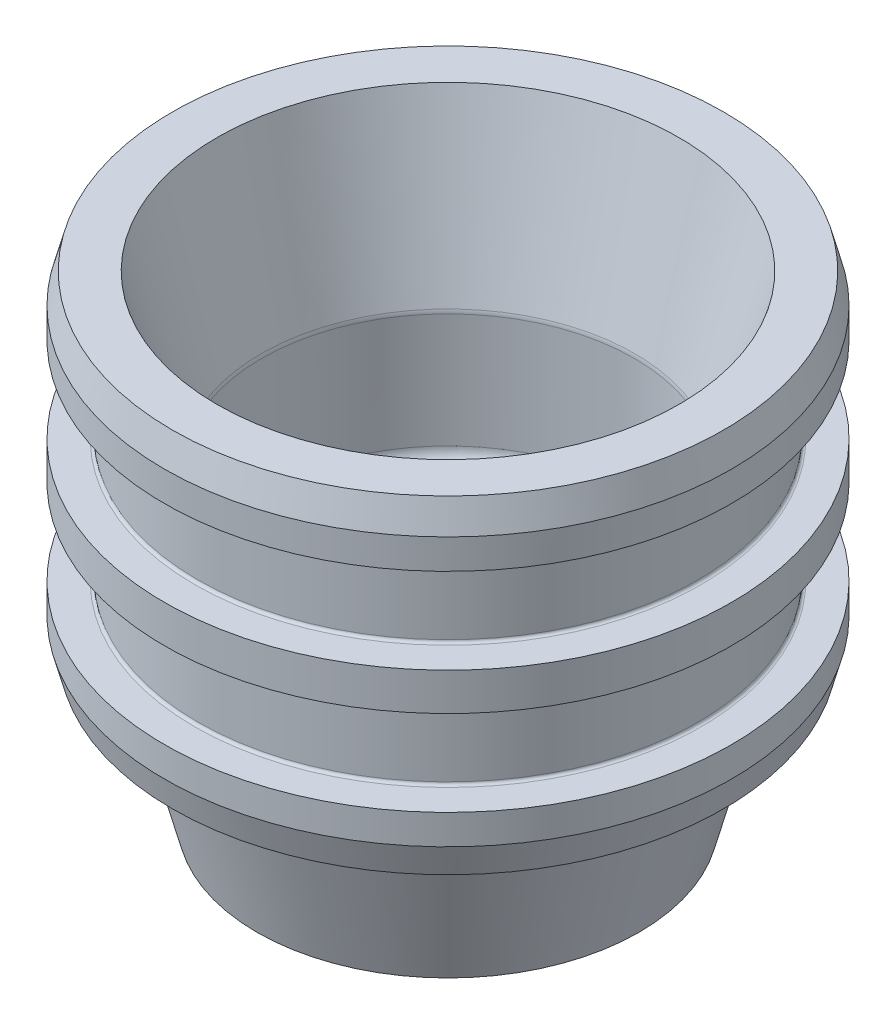
SolidWorks part; units mm, degrees
material "6063-T6"
ref_plane "Front Plane" through (0, 0, 0) normal (0, 0, 1) x (1, 0, 0)
ref_plane "Top Plane" through (0, 0, 0) normal (0, 1, 0) x (1, 0, 0)
ref_plane "Right Plane" through (0, 0, 0) normal (1, 0, 0) x (0, 0, -1)
sketch "Sketch1" plane through (0, 0, 0) normal (0, 1, 0) x (1, 0, 0)
  circle A0 centre (0, 0) radius 24.1554
  dimension "D1" = 48.3108
extrude "body" add sketch "Sketch1" along normal blind 40.64
sketch "Sketch2" plane through (0, 40.64, 0) normal (0, 1, 0) x (1, 0, 0)
  circle A0 centre (0, 0) radius 15.875
  dimension "D1" = 31.75
extrude "\"lightening hole\"" cut sketch "Sketch2" against normal blind 25.4
sketch "main-o-ring" plane through (0, 0, 0) normal (0, 0, 1) x (1, 0, 0)
  line L0 (0, 0) -> (0, 33.5592) construction
  line L1 (-24.1554, 35.56) -> (-24.1554, 28.2702)
  line L2 (-24.1554, 35.56) -> (-21.5508, 35.56)
  line L3 (-21.3106, 35.3198) -> (-21.3106, 28.5104)
  line L4 (-21.5508, 28.2702) -> (-24.1554, 28.2702)
  line L5 (24.1554, 40.64) -> (-24.1554, 40.64) construction
  line L6 (-22.7942, 40.64) -> (-24.1554, 35.56) construction
  line L7 (-24.1554, 35.56) -> (-24.1554, 40.64) construction
  line L8 (-24.1554, 40.64) -> (-22.7942, 40.64) construction
  arc A0 (-21.3106, 28.5104) -> (-21.5508, 28.2702) centre (-21.5508, 28.5104) cw
  arc A1 (-21.5508, 35.56) -> (-21.3106, 35.3198) centre (-21.5508, 35.3198) cw
  dimension "D5" = 0.2402
  dimension "D1" = 48.3108
  dimension "D2" = 7.2898
  dimension "D3" = 5.08
  dimension "D4" = 2.8448
  dimension "D6" = 15
  dimension "D7" = 5.08
revolve "o-ring-main (with backup rings)" cut sketch "main-o-ring" angle 360 about L0
chamfer "install-chamfer" distance 2.54 angle 15 1 edges at (0, 40.64, 24.1554) first distance on face at (0, 40.64, 24.1554)
chamfer "prop-chamfer" distance 3.81 angle 75 1 edges at (0, 40.64, 15.875) first distance on face at (0, 40.64, 23.4748)
ref_plane "mirror-plane" through (0, 26.67, 0) normal (0, 1, 0) x (1, 0, 0)
mirror "Top-Bottom Symmetry" about plane through (0, 26.67, 0) normal (0, 1, 0) of "o-ring-main (with backup rings)"
chamfer "bot-install-chamfer" [suppressed] distance 2.54 angle 15
chamfer "bot-prop-chamfer" [suppressed] distance 3.81 angle 75
hole_wizard "#6-32 Tapped Hole1" [suppressed] positions "3DSketch1" profile "Sketch3" tap size "#6-32" standard "ANSI Inch"
sketch3d "3DSketch1"
  point P0 (-24.1554, 7.9375, 0)
  dimension "D1" = 7.9375
sketch "Sketch3" plane through (-24.1554, 7.9375, 0) normal (0, 1, 0) x (0, 0, 1)
  line L0 (0, 0) -> (0, 8.7629)
  line L1 (0, 8.7629) -> (1.3525, 7.9502)
  line L2 (1.3525, 7.9502) -> (1.3525, 0)
  line L5 (1.3525, 0) -> (0, 0)
  line L10 (0, 8.7629) -> (-1.3526, 7.9502) construction
  line L11 (0, -6.35) -> (0, 107.95) construction
  dimension "Tap Drill Dia." = 2.7051
  dimension "Tap Drill Depth" = 7.9502
  dimension "Drill Angle" = 118
cosmetic thread "Hole Thread34" [suppressed] parameters "D1"=7.0104, "D2"=3.5052
ref_plane "Offset Reference" [suppressed] through (-22.3167, 0, -9.2439) normal (-0.9239, 0, -0.3827) x (0, -1, 0)
hole_wizard "#6-32 Tapped Hole2" [suppressed] positions "3DSketch2" profile "Sketch4" tap size "#6-32" standard "ANSI Inch"
sketch3d "3DSketch2" [suppressed]
  point P0 (-22.3167, -7.9375, -9.2439)
  dimension "D1" = 7.9375
sketch "Sketch4" plane through (-22.3167, -7.9375, -9.2439) normal (0, 1, 0) x (-0.3827, 0, 0.9239)
  line L0 (0, 0) -> (0, 8.7629)
  line L1 (0, 8.7629) -> (1.3525, 7.9502)
  line L2 (1.3525, 7.9502) -> (1.3525, 0)
  line L5 (1.3525, 0) -> (0, 0)
  line L10 (0, 8.7629) -> (-1.3526, 7.9502) construction
  line L11 (0, -6.35) -> (0, 107.95) construction
  dimension "Tap Drill Dia." = 2.7051
  dimension "Tap Drill Depth" = 7.9502
  dimension "Drill Angle" = 118
cosmetic thread "Hole Thread35" [suppressed] parameters "D1"=7.0104, "D2"=3.5052
pattern_circular "Tapped Hole Pattern" [suppressed] count 8 over 360
cosmetic thread "Hole Thread36" [suppressed] parameters "D1"=7.0104, "D2"=3.5052
cosmetic thread "Hole Thread37" [suppressed] parameters "D1"=7.0104, "D2"=3.5052
cosmetic thread "Hole Thread38" [suppressed] parameters "D1"=7.0104, "D2"=3.5052
cosmetic thread "Hole Thread39" [suppressed] parameters "D1"=7.0104, "D2"=3.5052
cosmetic thread "Hole Thread40" [suppressed] parameters "D1"=7.0104, "D2"=3.5052
cosmetic thread "Hole Thread41" [suppressed] parameters "D1"=7.0104, "D2"=3.5052
cosmetic thread "Hole Thread42" [suppressed] parameters "D1"=7.0104, "D2"=3.5052
cosmetic thread "Hole Thread43" [suppressed] parameters "D1"=7.0104, "D2"=3.5052
cosmetic thread "Hole Thread44" [suppressed] parameters "D1"=7.0104, "D2"=3.5052
cosmetic thread "Hole Thread45" [suppressed] parameters "D1"=7.0104, "D2"=3.5052
cosmetic thread "Hole Thread46" [suppressed] parameters "D1"=7.0104, "D2"=3.5052
cosmetic thread "Hole Thread47" [suppressed] parameters "D1"=7.0104, "D2"=3.5052
cosmetic thread "Hole Thread48" [suppressed] parameters "D1"=7.0104, "D2"=3.5052
cosmetic thread "Hole Thread49" [suppressed] parameters "D1"=7.0104, "D2"=3.5052
sketch "Sketch5" [suppressed] plane through (0, 38.1, 0) normal (0, 1, 0) x (1, 0, 0)
  circle A0 centre (0, 0) radius 24.1554
  dimension "D1" = 48.3108
extrude "top-reduce" [suppressed] cut sketch "Sketch5" against normal blind 12.7
chamfer "top-chamfer" [suppressed] distance 2.54 angle 45
sketch "Sketch6" plane through (0, 0, 0) normal (0, -1, 0) x (1, 0, 0)
  circle A0 centre (0, 0) radius 24.1554
  dimension "D1" = 48.3108
extrude "bottom-reduce" [suppressed] cut sketch "Sketch6" against normal blind 13.97
hole_wizard "1/4-20 (0.250) Piston Stop/Vent" [suppressed] positions "3DSketch3" profile "Sketch7" tap size "1/4-20" standard "ANSI Inch"
sketch3d "3DSketch3"
  point P0 (-24.1554, 0, 0)
sketch "Sketch7" plane through (-24.1554, 0, 0) normal (0, 1, 0) x (0, 0, 1)
  line L0 (0, 0) -> (0, 7.8838)
  line L1 (0, 7.8838) -> (2.5527, 6.35)
  line L2 (2.5527, 6.35) -> (2.5527, 0)
  line L5 (2.5527, 0) -> (0, 0)
  line L10 (0, 7.8838) -> (-2.5527, 6.35) construction
  line L11 (0, -6.35) -> (0, 107.95) construction
  dimension "Tap Drill Dia." = 5.1054
  dimension "Tap Drill Depth" = 6.35
  dimension "Drill Angle" = 118
cosmetic thread "Hole Thread17" [suppressed] parameters "D1"=7.62, "D2"=6.35
hole_wizard "5/16 (0.3125) Piston Bore" [suppressed] positions "3DSketch4" profile "Sketch8" hole size "23/64" standard "ANSI Inch"
sketch3d "3DSketch4"
  point P0 (24.1554, 0, 0)
sketch "Sketch8" plane through (24.1554, 0, 0) normal (0, 1, 0) x (0, 0, -1)
  line L0 (0, 0) -> (0, 48.3108)
  line L1 (0, 48.3108) -> (4.5641, 48.3108)
  line L2 (4.5641, 48.3108) -> (4.5641, 0)
  line L5 (4.5641, 0) -> (0, 0)
  line L11 (0, -6.35) -> (0, 107.95) construction
  dimension "Thru Hole Dia." = 9.1283
  dimension "Thru Hole Depth" = 48.3108
hole_wizard "3/8-16 Thread Blast Cap" [suppressed] positions "3DSketch6" profile "Sketch11" tap size "3/8-16" standard "ANSI Inch"
sketch3d "3DSketch6"
  point P0 (24.1554, 0, 0)
sketch "Sketch11" plane through (24.1554, 0, 0) normal (0, 1, 0) x (0, 0, -1)
  line L0 (0, 0) -> (0, 11.9097)
  line L1 (0, 11.9097) -> (3.9687, 9.525)
  line L2 (3.9687, 9.525) -> (3.9687, 0)
  line L5 (3.9687, 0) -> (0, 0)
  line L10 (0, 11.9097) -> (-3.9688, 9.525) construction
  line L11 (0, -6.35) -> (0, 107.95) construction
  dimension "Tap Drill Dia." = 7.9375
  dimension "Tap Drill Depth" = 9.525
  dimension "Drill Angle" = 118
hole_wizard "3/32 (0.09375) Press Inlet" [suppressed] positions "Sketch12" profile "Sketch14" hole size "3/32" standard "ANSI Inch"
sketch "Sketch12" plane through (0, 12.7, 0) normal (0, 1, 0) x (1, 0, 0)
  line L0 (0, 0) -> (-2.54, 0) construction
  point P0 (-2.54, 0)
  dimension "D1" = 2.54
sketch "Sketch14" plane through (-2.54, 12.7, 0) normal (1, 0, 0) x (0, 0, 1)
  line L0 (0, 0) -> (0, 8.8503)
  line L1 (0, 8.8503) -> (1.1906, 8.1349)
  line L2 (1.1906, 8.1349) -> (1.1906, 0)
  line L5 (1.1906, 0) -> (0, 0)
  line L10 (0, 8.8503) -> (-1.1906, 8.1349) construction
  line L11 (0, -6.35) -> (0, 107.95) construction
  dimension "Hole Dia." = 2.3812
  dimension "Hole Depth" = 8.1349
  dimension "Drill Angle" = 118
ref_plane "Vent Reference Plane" [suppressed] through (0, 0, -24.1554) normal (0, 0, -1) x (-1, 0, 0)
hole_wizard "3/32 (0.09375) Diameter Hole2" [suppressed] positions "Sketch16" profile "Sketch17" hole size "3/32" standard "ANSI Inch"
sketch "Sketch16" plane through (0, 0, -24.1554) normal (0, 0, -1) x (-1, 0, 0)
  line L2 (0, 0) -> (-12.9945, 0) construction
  point P0 (-10.16, 2.54)
  dimension "D1" = 2.54
  dimension "D2" = 10.16
sketch "Sketch17" plane through (10.16, 2.54, -24.1554) normal (1, 0, 0) x (0, 1, 0)
  line L0 (0, 0) -> (0, 22.9404)
  line L1 (0, 22.9404) -> (1.1906, 22.225)
  line L2 (1.1906, 22.225) -> (1.1906, 0)
  line L5 (1.1906, 0) -> (0, 0)
  line L10 (0, 22.9404) -> (-1.1906, 22.225) construction
  line L11 (0, -6.35) -> (0, 107.95) construction
  dimension "Hole Dia." = 2.3812
  dimension "Hole Depth" = 22.225
  dimension "Drill Angle" = 118
hole_wizard "1/4 (0.25) Diameter Hole1" [suppressed] positions "Sketch18" profile "Sketch20" hole size "1/4" standard "ANSI Inch"
sketch "Sketch18" plane through (0, 0, -24.1554) normal (0, 0, -1) x (-1, 0, 0)
  point P0 (0, 0)
sketch "Sketch20" plane through (0, 0, -24.1554) normal (1, 0, 0) x (0, 1, 0)
  line L0 (0, 0) -> (0, 27.3077)
  line L1 (0, 27.3077) -> (3.175, 25.4)
  line L2 (3.175, 25.4) -> (3.175, 0)
  line L5 (3.175, 0) -> (0, 0)
  line L10 (0, 27.3077) -> (-3.175, 25.4) construction
  line L11 (0, -6.35) -> (0, 107.95) construction
  dimension "Hole Dia." = 6.35
  dimension "Hole Depth" = 25.4
  dimension "Drill Angle" = 118
hole_wizard "3/4 (0.75) Diameter Hole1" [suppressed] positions "Sketch21" profile "Sketch22" hole size "3/4" standard "ANSI Inch"
sketch "Sketch21" plane through (0, 0, -24.1554) normal (0, 0, -1) x (-1, 0, 0)
  point P0 (0, 0)
sketch "Sketch22" plane through (0, 0, -24.1554) normal (1, 0, 0) x (0, 1, 0)
  line L0 (0, 0) -> (0, 37.4732)
  line L1 (0, 37.4732) -> (9.525, 31.75)
  line L2 (9.525, 31.75) -> (9.525, 0)
  line L5 (9.525, 0) -> (0, 0)
  line L10 (0, 37.4732) -> (-9.525, 31.75) construction
  line L11 (0, -6.35) -> (0, 107.95) construction
  dimension "Hole Dia." = 19.05
  dimension "Hole Depth" = 31.75
  dimension "Drill Angle" = 118
hole_wizard "1/4 (0.25) Diameter Hole2" [suppressed] positions "Sketch25" profile "Sketch26" hole size "1/4" standard "ANSI Inch"
sketch "Sketch25" plane through (0, 12.7, 0) normal (0, 1, 0) x (1, 0, 0)
  line L3 (0, 0) -> (0, -12.7) construction
  line L4 (4.8601, -11.7333) -> (0, -11.7333) construction
  line L6 (4.8601, -11.7333) -> (0, 0) construction
  circle A0 centre (0, 0) radius 12.7 construction
  point P0 (4.8601, -11.7333)
  dimension "D1" = 25.4
  dimension "D2" = 22.5
sketch "Sketch26" plane through (4.8601, 12.7, 11.7333) normal (1, 0, 0) x (0, 0, 1)
  line L0 (0, 0) -> (0, 24.13)
  line L1 (0, 24.13) -> (3.175, 24.13)
  line L2 (3.175, 24.13) -> (3.175, 0)
  line L5 (3.175, 0) -> (0, 0)
  line L11 (0, -6.35) -> (0, 107.95) construction
  dimension "Thru Hole Dia." = 6.35
  dimension "Thru Hole Depth" = 49.53
ref_plane "Valve Stem Reference Plane" [suppressed] through (-24.1554, 0, 0) normal (-1, 0, 0) x (0, 0, 1)
hole_wizard "3/8 (0.375) Diameter Hole1" [suppressed] positions "Sketch27" profile "Sketch28" hole size "3/8" standard "ANSI Inch"
sketch "Sketch27" plane through (-24.1554, 0, 0) normal (-1, 0, 0) x (0, 0, 1)
  point P0 (0, 0)
sketch "Sketch28" plane through (-24.1554, 0, 0) normal (0, 1, 0) x (0, 0, 1)
  line L0 (0, 0) -> (0, 28.2616)
  line L1 (0, 28.2616) -> (4.7625, 25.4)
  line L2 (4.7625, 25.4) -> (4.7625, 0)
  line L5 (4.7625, 0) -> (0, 0)
  line L10 (0, 28.2616) -> (-4.7625, 25.4) construction
  line L11 (0, -6.35) -> (0, 107.95) construction
  dimension "Hole Dia." = 9.525
  dimension "Hole Depth" = 25.4
  dimension "Drill Angle" = 118
hole_wizard "1/8-27 NPSM Tapped Hole2" [suppressed] positions "Sketch31" profile "Sketch32" tap size "1/8-27 NPSM" standard "ANSI Inch"
sketch "Sketch31" [suppressed] plane through (0, -11.43, 0) normal (0, -1, 0) x (-1, 0, 0)
  point P0 (0, 0)
sketch "Sketch32" plane through (0, -11.43, 0) normal (1, 0, 0) x (0, 0, -1)
  line L0 (0, 0) -> (0, 12.2569)
  line L1 (0, 12.2569) -> (4.5466, 9.525)
  line L2 (4.5466, 9.525) -> (4.5466, 0)
  line L5 (4.5466, 0) -> (0, 0)
  line L10 (0, 12.2569) -> (-4.5466, 9.525) construction
  line L11 (0, -6.35) -> (0, 107.95) construction
  dimension "Tap Drill Dia." = 9.0932
  dimension "Tap Drill Depth" = 9.525
  dimension "Drill Angle" = 118
hole_wizard "11/32 (0.34375) Diameter Hole1" [suppressed] positions "Sketch33" profile "Sketch35" hole size "11/32" standard "ANSI Inch"
sketch "Sketch33" [suppressed] plane through (0, -11.43, 0) normal (0, -1, 0) x (-1, 0, 0)
  point P0 (0, 0)
sketch "Sketch35" plane through (0, -11.43, 0) normal (1, 0, 0) x (0, 0, -1)
  line L0 (0, 0) -> (0, 36.83)
  line L1 (0, 36.83) -> (4.3656, 36.83)
  line L2 (4.3656, 36.83) -> (4.3656, 0)
  line L5 (4.3656, 0) -> (0, 0)
  line L11 (0, -6.35) -> (0, 107.95) construction
  dimension "Thru Hole Dia." = 8.7312
  dimension "Thru Hole Depth" = 36.83
chamfer "bottom-chamfer" [suppressed] distance 1.27 angle 45
sketch "Sketch36" [suppressed] plane through (0, -22.86, 0) normal (0, -1, 0) x (1, 0, 0)
  circle A0 centre (0, 0) radius 19.05
  circle A1 centre (0, 0) radius 22.8854 construction
  dimension "D1" = 38.1
extrude "bot-extrude" [suppressed] cut sketch "Sketch36" against normal blind 38.1
chamfer "Chamfer3" [suppressed] distance 1.27 angle 45
fillet "Fillet1" [suppressed] radius 1.27
chamfer "Chamfer4" [suppressed] distance 1.27 angle 45
sketch "Sketch37" [suppressed] plane through (0, 12.7, 0) normal (0, 1, 0) x (1, 0, 0)
  circle A0 centre (0, 0) radius 25.4
  dimension "D1" = 50.8
extrude "Cut-Extrude1" [suppressed] cut sketch "Sketch37" against normal blind 16.51
chamfer "Chamfer5" [suppressed] distance 1.27 angle 45
hole_wizard "1/8-27 NPSM Tapped Hole1" [suppressed] positions "Sketch38" profile "Sketch39" tap size "1/8-27 NPSM" standard "ANSI Inch"
sketch "Sketch38" plane through (0, -3.81, 0) normal (0, 1, 0) x (1, 0, 0)
  point P0 (0, 0)
sketch "Sketch39" plane through (0, -3.81, 0) normal (1, 0, 0) x (0, 0, 1)
  line L0 (0, 0) -> (0, 25.7189)
  line L1 (0, 25.7189) -> (4.5466, 22.987)
  line L2 (4.5466, 22.987) -> (4.5466, 0)
  line L5 (4.5466, 0) -> (0, 0)
  line L10 (0, 25.7189) -> (-4.5466, 22.987) construction
  line L11 (0, -6.35) -> (0, 107.95) construction
  dimension "Tap Drill Dia." = 9.0932
  dimension "Tap Drill Depth" = 22.987
  dimension "Drill Angle" = 118
cosmetic thread "Hole Thread50" [suppressed] parameters "D1"=20.1676, "D2"=10.0932
hole_wizard "1/8-27 NPSM Tapped Hole3" [suppressed] positions "Sketch40" profile "Sketch42" tap size "1/8-27 NPSM" standard "ANSI Inch"
sketch "Sketch40" [suppressed] plane through (0, -12.7, 0) normal (0, -1, 0) x (-1, 0, 0)
  point P0 (0, 0)
sketch "Sketch42" plane through (0, -12.7, 0) normal (1, 0, 0) x (0, 0, -1)
  line L0 (0, 0) -> (0, 9.0819)
  line L1 (0, 9.0819) -> (4.5466, 6.35)
  line L2 (4.5466, 6.35) -> (4.5466, 0)
  line L5 (4.5466, 0) -> (0, 0)
  line L10 (0, 9.0819) -> (-4.5466, 6.35) construction
  line L11 (0, -6.35) -> (0, 107.95) construction
  dimension "Tap Drill Dia." = 9.0932
  dimension "Tap Drill Depth" = 6.35
  dimension "Drill Angle" = 118
cosmetic thread "Hole Thread51" [suppressed] parameters "D1"=20.1676, "D2"=10.0838
hole_wizard "1/8-27 NPSM Tapped Hole4" [suppressed] positions "Sketch43" profile "Sketch44" tap size "1/8-27 NPSM" standard "ANSI Inch"
sketch "Sketch43" plane through (0, 12.7, 0) normal (0, 1, 0) x (1, 0, 0)
  circle A0 centre (0, 0) radius 16.282 construction
  point P0 (-10.16, 0)
  dimension "D1" = 10.16
sketch "Sketch44" plane through (-10.16, 12.7, 0) normal (1, 0, 0) x (0, 0, 1)
  line L0 (0, 0) -> (0, 12.2569)
  line L1 (0, 12.2569) -> (4.5466, 9.525)
  line L2 (4.5466, 9.525) -> (4.5466, 0)
  line L5 (4.5466, 0) -> (0, 0)
  line L10 (0, 12.2569) -> (-4.5466, 9.525) construction
  line L11 (0, -6.35) -> (0, 107.95) construction
  dimension "Tap Drill Dia." = 9.0932
  dimension "Tap Drill Depth" = 9.525
  dimension "Drill Angle" = 118
cosmetic thread "Hole Thread52" [suppressed] parameters "D1"=20.1676, "D2"=10.0838
hole_wizard "1/8 (0.125) Diameter Hole1" [suppressed] positions "Sketch45" profile "Sketch47" hole size "1/8" standard "ANSI Inch"
sketch "Sketch45" plane through (0, 12.7, 0) normal (0, 1, 0) x (1, 0, 0)
  circle A0 centre (0, 0) radius 16.282 construction
  point P0 (-10.16, 0)
  dimension "D1" = 10.16
sketch "Sketch47" plane through (-10.16, 12.7, 0) normal (1, 0, 0) x (0, 0, 1)
  line L0 (0, 0) -> (0, 24.13)
  line L1 (0, 24.13) -> (1.5875, 24.13)
  line L2 (1.5875, 24.13) -> (1.5875, 0)
  line L5 (1.5875, 0) -> (0, 0)
  line L11 (0, -6.35) -> (0, 107.95) construction
  dimension "Thru Hole Dia." = 3.175
  dimension "Thru Hole Depth" = 24.13
hole_wizard "1/8 (0.125) Diameter Hole2" [suppressed] positions "Sketch48" profile "Sketch49" hole size "1/8" standard "ANSI Inch"
sketch "Sketch48" plane through (0, -3.81, 0) normal (0, 1, 0) x (1, 0, 0)
  circle A0 centre (0, 0) radius 22.8854 construction
  point P0 (-15.24, 0)
  dimension "D1" = 15.24
sketch "Sketch49" plane through (-15.24, -3.81, 0) normal (1, 0, 0) x (0, 0, 1)
  line L0 (0, 0) -> (0, 21.59)
  line L1 (0, 21.59) -> (1.5875, 21.59)
  line L2 (1.5875, 21.59) -> (1.5875, 0)
  line L5 (1.5875, 0) -> (0, 0)
  line L11 (0, -6.35) -> (0, 107.95) construction
  dimension "Thru Hole Dia." = 3.175
  dimension "Thru Hole Depth" = 21.59
hole_wizard "1/8-27 NPSM Tapped Hole5" [suppressed] positions "Sketch52" profile "Sketch53" tap size "1/8-27 NPSM" standard "ANSI Inch"
sketch "Sketch52" plane through (0, -3.81, 0) normal (0, 1, 0) x (1, 0, 0)
  circle A0 centre (0, 0) radius 22.8854 construction
  point P0 (-15.24, 0)
  dimension "D1" = 15.24
cosmetic thread "Hole Thread53" [suppressed] parameters "D1"=8.5852, "D2"=10.0838
sketch "Sketch53" plane through (-15.24, -3.81, 0) normal (1, 0, 0) x (0, 0, 1)
  line L0 (0, 0) -> (0, 9.525)
  line L1 (0, 9.525) -> (4.5466, 6.7931)
  line L2 (4.5466, 6.7931) -> (4.5466, 0)
  line L5 (4.5466, 0) -> (0, 0)
  line L10 (0, 9.525) -> (-4.5466, 6.7931) construction
  line L11 (0, -6.35) -> (0, 107.95) construction
  dimension "Tap Drill Dia." = 9.0932
  dimension "Tap Drill Depth" = 9.525
  dimension "Drill Angle" = 118
sketch "Sketch54" plane through (0, 0, 0) normal (0, -1, 0) x (1, 0, 0)
  circle A0 centre (0, 0) radius 15.875
  circle A4 centre (0, 0) radius 24.1554
  circle A5 centre (0, 0) radius 24.1554
  dimension "D1" = 31.75
  dimension "D2" = 0
extrude "conform-cut" cut sketch "Sketch54" against normal blind 12.7
chamfer "bottom-press-draft" distance 3.81 angle 75 1 edges at (0, 12.7, -15.875) first distance on face at (0, 12.7, -15.875)
fillet "edge-breaks" radius 1.27 2 edges at (0, 26.4209, 15.875) (0, 15.24, 15.875)
chamfer "install-chamfer-2" distance 2.54 angle 15 1 edges at (0, 12.7, -24.1554) first distance on face at (0, 17.78, -24.1554)
